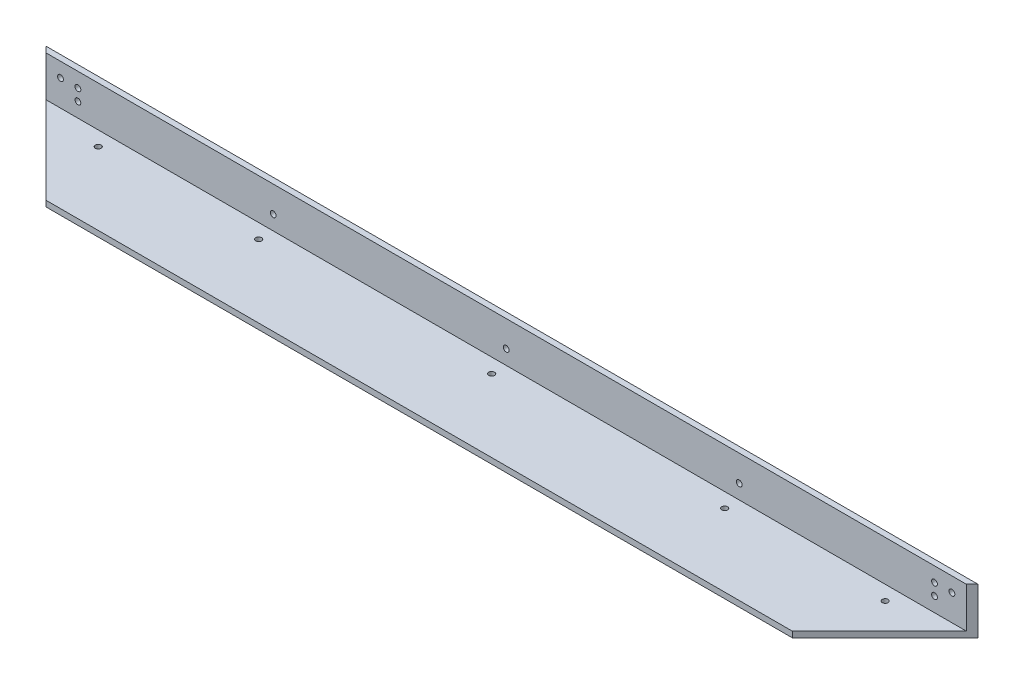
SolidWorks part; units mm, degrees
ref_plane "Front Plane" through (0, 0, 0) normal (0, 0, 1) x (1, 0, 0)
ref_plane "Top Plane" through (0, 0, 0) normal (0, 1, 0) x (1, 0, 0)
ref_plane "Right Plane" through (0, 0, 0) normal (1, 0, 0) x (0, 0, -1)
sketch "Sketch1" plane through (0, 0, 0) normal (1, 0, 0) x (0, 0, -1)
  line L0 (0, 0) -> (-50.8, 0)
  line L1 (-50.8, 0) -> (-50.8, 3.175)
  line L2 (-50.8, 3.175) -> (-3.175, 3.175)
  line L3 (-3.175, 3.175) -> (-3.175, 25.4)
  line L4 (-3.175, 25.4) -> (0, 25.4)
  line L5 (0, 25.4) -> (0, 0)
  dimension "LHeight" = 25.4
  dimension "LWidth" = 50.8
  dimension "LMaterialThickness" = 3.175
  dimension "D1" = 47.625
  dimension "D2" = 22.225
  dimension "D3" = 3.175
extrude "Boss-Extrude1" add sketch "Sketch1" along normal blind 510
chamfer "Chamfer6" distance 50.8 angle 45 1 edges at (510, 1.5875, 50.8)
chamfer "Chamfer7" distance 50.8 angle 45 1 edges at (0, 1.5875, 50.8)
sketch "FrontSideHoles-Sketch2" plane through (0, 0, 0) normal (0, 0, -1) x (-1, 0, 0)
  line L0 (0, 0) -> (0, 25.4) construction
  line L1 (-510, 0) -> (0, 0) construction
  line L2 (-510, 0) -> (-510, 25.4) construction
  circle A0 centre (-498.8875, 17.4625) radius 1.5875
  circle A1 centre (-489.3625, 17.4625) radius 1.5875
  circle A2 centre (-20.6375, 17.4625) radius 1.5875
  circle A3 centre (-11.1125, 17.4625) radius 1.5875
  circle A5 centre (-20.6375, 11.1125) radius 1.5875
  circle A6 centre (-489.3625, 11.1125) radius 1.5875
  circle A8 centre (-382.5, 11.1125) radius 1.5875
  circle A9 centre (-255, 11.1125) radius 1.5875
  circle A10 centre (-127.5, 11.1125) radius 1.5875
  dimension "D5" = 3.175
  dimension "D1" = 11.1125
  dimension "D2" = 20.6375
  dimension "D3" = 11.1125
  dimension "D4" = 20.6375
  dimension "D6" = 7.9375
  dimension "D8" = 127.5
  dimension "D9" = 127.5
  dimension "D10" = 127.5
  dimension "D7" = 11.1125
extrude "FrontSideHoles-Cut-Extrude2" cut sketch "FrontSideHoles-Sketch2" against normal through all
sketch "BottomHoles-Sketch2" plane through (0, 0, 0) normal (0, -1, 0) x (1, 0, 0)
  line L0 (510, 0) -> (0, 0) construction
  circle A0 centre (39.6875, 11.1125) radius 1.5875
  circle A1 centre (470.3125, 11.1125) radius 1.5875
  circle A2 centre (127.5, 11.1125) radius 1.5875
  circle A3 centre (255, 11.1125) radius 1.5875
  circle A4 centre (382.5, 11.1125) radius 1.5875
  dimension "D1" = 11.1125
  dimension "D4" = 3.175
  dimension "D2" = 39.6875
  dimension "D3" = 39.6875
  dimension "D5" = 127.5
  dimension "D6" = 127.5
  dimension "D7" = 127.5
extrude "BottomHoles-Cut-Extrude1" cut sketch "BottomHoles-Sketch2" against normal through all
equation "\"LowerRailWidth\"= 2.00in"
equation "\"LowerRailHeight\"= 1.00in"
equation "\"RailThickness\"= .125in'Spec"
equation "\"SideRailHoleX1FromSide\"= \"HoleOffsetFromSide\""
equation "\"SideRailHoleX2FromSide\"= \"VSWidth\" - \"HoleOffsetFromEdge\" - \"RailThickness\"'Equals 20.6375"
equation "\"SideRailHoleY1FromEdge\"= \"HoleOffsetFromEdge\""
equation "\"FrontBackRailLength\"= 510mm"
equation "\"VSWidth\"= 1.25in'Spec"
equation "\"HoleOffsetFromEdge\"= \"RailThickness\" * 2.5"
equation "\"HoleOffsetFromSide\"= \"RailThickness\" * 3.5"
equation "\"SideRailHoleY2FromSide\"= \"HoleOffsetFromSide\""
equation "\"FasteningHoleDiameter\"= .125in"
equation "\"D1@Boss-Extrude1\"=\"FrontBackRailLength\""
equation "\"D1@Chamfer6\"=\"LowerRailWidth\""
equation "\"D1@Chamfer7\"=\"LowerRailWidth\""
equation "\"D1@FrontSideHoles-Sketch2\" = \"SideRailHoleX1FromSide\""
equation "\"D2@FrontSideHoles-Sketch2\" = \"SideRailHoleX2FromSide\""
equation "\"D3@FrontSideHoles-Sketch2\" = \"SideRailHoleX1FromSide\""
equation "\"D4@FrontSideHoles-Sketch2\" = \"SideRailHoleX2FromSide\""
equation "\"D5@FrontSideHoles-Sketch2\" = \"FasteningHoleDiameter\""
equation "\"D6@FrontSideHoles-Sketch2\" = \"SideRailHoleY1FromEdge\""
equation "\"LHeight@Sketch1\"=\"LowerRailHeight\""
equation "\"LWidth@Sketch1\"=\"LowerRailWidth\""
equation "\"LowerCornerBlockWidth\"= \"LowerRailWidth\" - \"RailThickness\" * 2'Room for left front stepper"
equation "\"D1@BottomHoles-Sketch2\"=\"LowerCornerBlockY1FromSide\""
equation "\"D2@BottomHoles-Sketch2\"=\"LowerCornerBlockX1FromSide\""
equation "\"D3@BottomHoles-Sketch2\"=\"LowerCornerBlockX1FromSide\""
equation "\"D4@BottomHoles-Sketch2\" = \"FasteningHoleDiameter\""
equation "\"LowerCornerBlockX1FromSide\"= \"LowerCornerBlockWidth\" - \"HoleOffsetFromEdge\" + \"RailThickness\""
equation "\"LowerCornerBlockY1FromSide\"= \"HoleOffsetFromSide\""
equation "\"FrontOrBackEnclosureOffsets\"= \"FrontBackRailLength\" / 4"
equation "\"D5@BottomHoles-Sketch2\"=\"FrontOrBackEnclosureOffsets\""
equation "\"D6@BottomHoles-Sketch2\"=\"FrontOrBackEnclosureOffsets\""
equation "\"D7@BottomHoles-Sketch2\"=\"FrontOrBackEnclosureOffsets\""
equation "\"D8@FrontSideHoles-Sketch2\"=\"FrontOrBackEnclosureOffsets\""
equation "\"D9@FrontSideHoles-Sketch2\"=\"FrontOrBackEnclosureOffsets\""
equation "\"D10@FrontSideHoles-Sketch2\"=\"FrontOrBackEnclosureOffsets\""
equation "\"D7@FrontSideHoles-Sketch2\"=\"SideRailHoleY2FromSide\""
